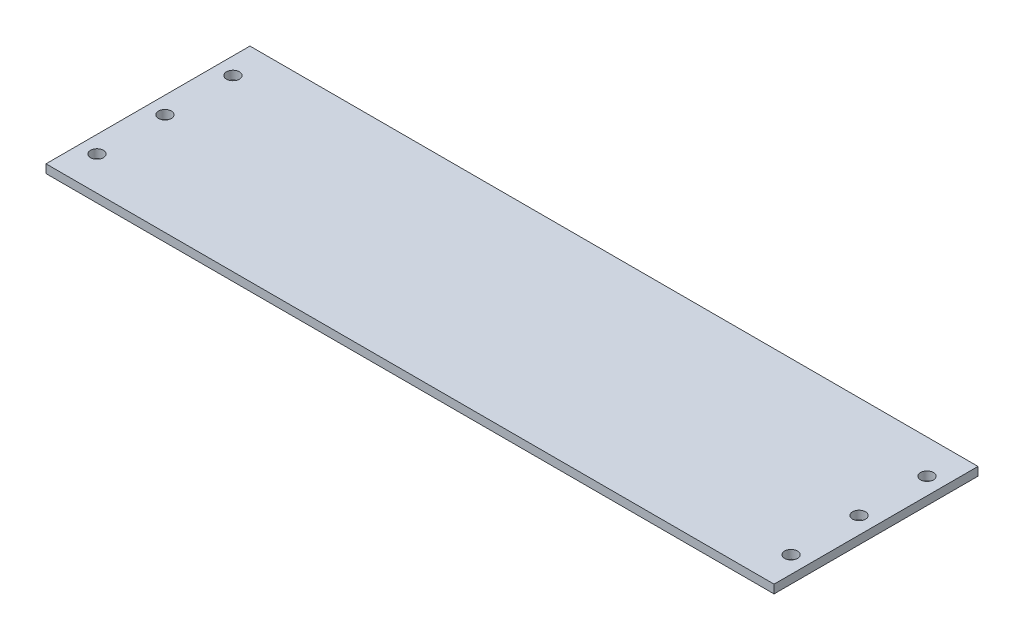
SolidWorks part; units mm, degrees
ref_plane "Front Plane" through (0, 0, 0) normal (0, 0, 1) x (1, 0, 0)
ref_plane "Top Plane" through (0, 0, 0) normal (0, 1, 0) x (1, 0, 0)
ref_plane "Right Plane" through (0, 0, 0) normal (1, 0, 0) x (0, 0, -1)
sketch "Sketch1" plane through (0, 0, 0) normal (0, 1, 0) x (1, 0, 0)
  line L0 (0, 38.1) -> (272.034, 38.1) construction
  line L1 (0, 0) -> (272.034, 0)
  line L2 (0, 0) -> (0, 76.2)
  line L3 (0, 76.2) -> (272.034, 76.2)
  line L4 (272.034, 0) -> (272.034, 76.2)
  line L5 (0, 63.5) -> (6.35, 63.5) construction
  line L6 (6.35, 63.5) -> (6.35, 12.7) construction
  line L7 (136.017, 76.2) -> (136.017, 0) construction
  line L8 (6.35, 63.5) -> (265.684, 63.5) construction
  circle A0 centre (6.35, 63.5) radius 2.413
  circle A1 centre (6.35, 38.1) radius 2.413
  circle A2 centre (6.35, 12.7) radius 2.413
  circle A3 centre (265.684, 12.7) radius 2.413
  circle A4 centre (265.684, 38.1) radius 2.413
  circle A5 centre (265.684, 63.5) radius 2.413
  dimension "D3" = 4.826
  dimension "D6" = 12.7
  dimension "D1" = 259.334
  dimension "D2" = 76.2
  dimension "D5" = 6.35
  dimension "D4" = 3
extrude "Boss-Extrude1" add sketch "Sketch1" along normal blind 3.175
